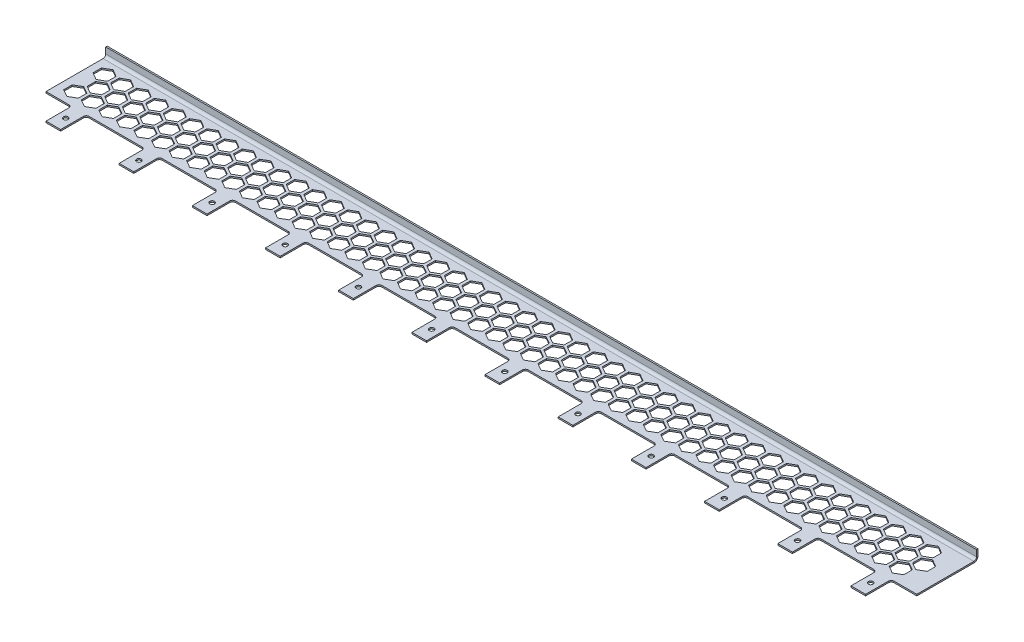
SolidWorks part; units mm, degrees
note: The reader was unsure of these and kept them because the rebuilt part matched: flange length of "Edge-Flange1".
ref_plane "Front Plane" through (0, 0, 0) normal (0, 0, 1) x (1, 0, 0)
ref_plane "Top Plane" through (0, 0, 0) normal (0, 1, 0) x (1, 0, 0)
ref_plane "Right Plane" through (0, 0, 0) normal (1, 0, 0) x (0, 0, -1)
sketch "Sketch1" plane through (0, 0, 0) normal (0, 1, 0) x (1, 0, 0)
  line L0 (29.5, 0) -> (65.5, 0)
  line L1 (0, 0) -> (15.5, 0)
  line L2 (0, 0) -> (0, 39)
  line L3 (0, 39) -> (595, 39)
  line L4 (595, 0) -> (595, 39)
  line L6 (17.5, -2) -> (17.5, -17.5)
  line L7 (17.5, -17.5) -> (27.5, -17.5)
  line L8 (27.5, -2) -> (27.5, -17.5)
  line L9 (67.5, -2) -> (67.5, -17.5)
  line L10 (67.5, -17.5) -> (77.5, -17.5)
  line L11 (77.5, -2) -> (77.5, -17.5)
  line L12 (117.5, -2) -> (117.5, -17.5)
  line L13 (117.5, -17.5) -> (127.5, -17.5)
  line L14 (127.5, -2) -> (127.5, -17.5)
  line L15 (167.5, -2) -> (167.5, -17.5)
  line L16 (167.5, -17.5) -> (177.5, -17.5)
  line L17 (177.5, -2) -> (177.5, -17.5)
  line L18 (217.5, -2) -> (217.5, -17.5)
  line L19 (217.5, -17.5) -> (227.5, -17.5)
  line L20 (227.5, -2) -> (227.5, -17.5)
  line L21 (267.5, -2) -> (267.5, -17.5)
  line L22 (267.5, -17.5) -> (277.5, -17.5)
  line L23 (277.5, -2) -> (277.5, -17.5)
  line L24 (317.5, -2) -> (317.5, -17.5)
  line L25 (317.5, -17.5) -> (327.5, -17.5)
  line L26 (327.5, -2) -> (327.5, -17.5)
  line L27 (367.5, -2) -> (367.5, -17.5)
  line L28 (367.5, -17.5) -> (377.5, -17.5)
  line L29 (377.5, -2) -> (377.5, -17.5)
  line L30 (417.5, -2) -> (417.5, -17.5)
  line L31 (417.5, -17.5) -> (427.5, -17.5)
  line L32 (427.5, -2) -> (427.5, -17.5)
  line L33 (467.5, -2) -> (467.5, -17.5)
  line L34 (467.5, -17.5) -> (477.5, -17.5)
  line L35 (477.5, -2) -> (477.5, -17.5)
  line L36 (517.5, -2) -> (517.5, -17.5)
  line L37 (517.5, -17.5) -> (527.5, -17.5)
  line L38 (527.5, -2) -> (527.5, -17.5)
  line L39 (567.5, -2) -> (567.5, -17.5)
  line L40 (567.5, -17.5) -> (577.5, -17.5)
  line L41 (577.5, -2) -> (577.5, -17.5)
  line L42 (79.5, 0) -> (115.5, 0)
  line L43 (129.5, 0) -> (165.5, 0)
  line L44 (179.5, 0) -> (215.5, 0)
  line L45 (229.5, 0) -> (265.5, 0)
  line L46 (279.5, 0) -> (315.5, 0)
  line L47 (329.5, 0) -> (365.5, 0)
  line L48 (379.5, 0) -> (415.5, 0)
  line L49 (429.5, 0) -> (465.5, 0)
  line L50 (479.5, 0) -> (515.5, 0)
  line L51 (529.5, 0) -> (565.5, 0)
  line L52 (579.5, 0) -> (595, 0)
  line L53 (22.5, -17.5) -> (22.5, 39) construction
  arc A0 (29.5, 0) -> (27.5, -2) centre (29.5, -2) ccw
  arc A1 (15.5, 0) -> (17.5, -2) centre (15.5, -2) cw
  arc A2 (79.5, 0) -> (77.5, -2) centre (79.5, -2) ccw
  arc A3 (65.5, 0) -> (67.5, -2) centre (65.5, -2) cw
  arc A4 (129.5, 0) -> (127.5, -2) centre (129.5, -2) ccw
  arc A5 (115.5, 0) -> (117.5, -2) centre (115.5, -2) cw
  arc A6 (179.5, 0) -> (177.5, -2) centre (179.5, -2) ccw
  arc A7 (165.5, 0) -> (167.5, -2) centre (165.5, -2) cw
  arc A8 (229.5, 0) -> (227.5, -2) centre (229.5, -2) ccw
  arc A9 (215.5, 0) -> (217.5, -2) centre (215.5, -2) cw
  arc A10 (279.5, 0) -> (277.5, -2) centre (279.5, -2) ccw
  arc A11 (265.5, 0) -> (267.5, -2) centre (265.5, -2) cw
  arc A12 (329.5, 0) -> (327.5, -2) centre (329.5, -2) ccw
  arc A13 (315.5, 0) -> (317.5, -2) centre (315.5, -2) cw
  arc A14 (379.5, 0) -> (377.5, -2) centre (379.5, -2) ccw
  arc A15 (365.5, 0) -> (367.5, -2) centre (365.5, -2) cw
  arc A16 (429.5, 0) -> (427.5, -2) centre (429.5, -2) ccw
  arc A17 (415.5, 0) -> (417.5, -2) centre (415.5, -2) cw
  arc A18 (479.5, 0) -> (477.5, -2) centre (479.5, -2) ccw
  arc A19 (465.5, 0) -> (467.5, -2) centre (465.5, -2) cw
  arc A20 (529.5, 0) -> (527.5, -2) centre (529.5, -2) ccw
  arc A21 (515.5, 0) -> (517.5, -2) centre (515.5, -2) cw
  arc A22 (579.5, 0) -> (577.5, -2) centre (579.5, -2) ccw
  arc A23 (565.5, 0) -> (567.5, -2) centre (565.5, -2) cw
  circle A24 centre (22.5, -9) radius 1.6
  circle A25 centre (72.5, -9) radius 1.6
  circle A26 centre (122.5, -9) radius 1.6
  circle A27 centre (172.5, -9) radius 1.6
  circle A28 centre (222.5, -9) radius 1.6
  circle A29 centre (272.5, -9) radius 1.6
  circle A30 centre (322.5, -9) radius 1.6
  circle A31 centre (372.5, -9) radius 1.6
  circle A32 centre (422.5, -9) radius 1.6
  circle A33 centre (472.5, -9) radius 1.6
  circle A34 centre (522.5, -9) radius 1.6
  circle A35 centre (572.5, -9) radius 1.6
  point P9 (22.5, -17.5)
  point P14 (17.5, 0)
  dimension "D6" = 2
  dimension "D8" = 9
  dimension "D9" = 3.2
  dimension "D1" = 595
  dimension "D2" = 39
  dimension "D3" = 10
  dimension "D4" = 17.5
  dimension "D5" = 22.5
  dimension "D7" = 12
  dimension "D10" = 12
base flange "Base-Flange2" sketch "Sketch1" thickness 1 reverse thickness direction no parameters "D1"=1.8
edge flange "Edge-Flange1" sketch "Sketch14" flange angle 90 flange length 7 flange position bend outside bend radius 1.8 thickness 1 relief rectangular parameters "D6"=10
sketch "Sketch14" plane through (0, 0, -39) normal (0, 0, -1) x (-1, 0, 0)
  line L0 (-595, 0) -> (0, 0) construction
  line L1 (-595, 0) -> (0, 0)
  line L2 (-595, 0) -> (-595, 6)
  line L3 (-595, 6) -> (0, 6)
  line L4 (0, 6) -> (0, 0)
bend "EdgeBend1" bend radius 1.8 bend angle 90 parameters "D5"=1
sketch "Sketch15" plane through (0, 0, 0) normal (0, 1, 0) x (1, 0, 0)
  line L0 (0, 0) -> (15.5, 0) construction
  line L1 (10, 4.2265) -> (15, 7.1132)
  line L2 (15, 7.1132) -> (15, 12.8868)
  line L3 (15, 12.8868) -> (10, 15.7735)
  line L4 (10, 15.7735) -> (5, 12.8868)
  line L5 (5, 12.8868) -> (5, 7.1132)
  line L6 (5, 7.1132) -> (10, 4.2265)
  line L7 (0, 39) -> (0, 0) construction
  line L8 (21.9375, 24.2268) -> (26.9685, 27.0592)
  line L9 (15.9823, 14.2265) -> (20.9911, 17.098)
  line L10 (20.9911, 17.098) -> (21.0088, 22.8714)
  line L11 (21.0088, 22.8714) -> (16.0177, 25.7735)
  line L12 (16.0177, 25.7735) -> (11.0089, 22.902)
  line L13 (11.0089, 22.902) -> (10.9912, 17.1286)
  line L14 (10.9912, 17.1286) -> (15.9823, 14.2265)
  line L15 (9.9375, 24.2268) -> (14.9685, 27.0592)
  line L16 (14.9685, 27.0592) -> (15.0311, 32.8324)
  line L17 (15.0311, 32.8324) -> (10.0627, 35.7732)
  line L18 (10.0627, 35.7732) -> (5.0317, 32.9408)
  line L19 (5.0317, 32.9408) -> (4.9691, 27.1676)
  line L20 (4.9691, 27.1676) -> (9.9375, 24.2268)
  line L21 (26.9685, 27.0592) -> (27.0311, 32.8324)
  line L22 (27.0311, 32.8324) -> (22.0627, 35.7732)
  line L23 (22.0627, 35.7732) -> (17.0317, 32.9408)
  line L24 (17.0317, 32.9408) -> (16.9691, 27.1676)
  line L25 (16.9691, 27.1676) -> (21.9375, 24.2268)
  line L26 (27.9823, 14.2265) -> (32.9911, 17.098)
  line L27 (32.9911, 17.098) -> (33.0088, 22.8714)
  line L28 (33.0088, 22.8714) -> (28.0177, 25.7735)
  line L29 (28.0177, 25.7735) -> (23.0089, 22.902)
  line L30 (23.0089, 22.902) -> (22.9912, 17.1286)
  line L31 (22.9912, 17.1286) -> (27.9823, 14.2265)
  line L32 (22, 4.2265) -> (27, 7.1132)
  line L33 (27, 7.1132) -> (27, 12.8868)
  line L34 (27, 12.8868) -> (22, 15.7735)
  line L35 (22, 15.7735) -> (17, 12.8868)
  line L36 (17, 12.8868) -> (17, 7.1132)
  line L37 (17, 7.1132) -> (22, 4.2265)
  line L38 (33.9375, 24.2268) -> (38.9685, 27.0592)
  line L39 (38.9685, 27.0592) -> (39.0311, 32.8324)
  line L40 (39.0311, 32.8324) -> (34.0627, 35.7732)
  line L41 (34.0627, 35.7732) -> (29.0317, 32.9408)
  line L42 (29.0317, 32.9408) -> (28.9691, 27.1676)
  line L43 (28.9691, 27.1676) -> (33.9375, 24.2268)
  line L44 (39.9823, 14.2265) -> (44.9911, 17.098)
  line L45 (44.9911, 17.098) -> (45.0088, 22.8714)
  line L46 (45.0088, 22.8714) -> (40.0177, 25.7735)
  line L47 (40.0177, 25.7735) -> (35.0089, 22.902)
  line L48 (35.0089, 22.902) -> (34.9912, 17.1286)
  line L49 (34.9912, 17.1286) -> (39.9823, 14.2265)
  line L50 (34, 4.2265) -> (39, 7.1132)
  line L51 (39, 7.1132) -> (39, 12.8868)
  line L52 (39, 12.8868) -> (34, 15.7735)
  line L53 (34, 15.7735) -> (29, 12.8868)
  line L54 (29, 12.8868) -> (29, 7.1132)
  line L55 (29, 7.1132) -> (34, 4.2265)
  line L56 (45.9375, 24.2268) -> (50.9685, 27.0592)
  line L57 (50.9685, 27.0592) -> (51.0311, 32.8324)
  line L58 (51.0311, 32.8324) -> (46.0627, 35.7732)
  line L59 (46.0627, 35.7732) -> (41.0317, 32.9408)
  line L60 (41.0317, 32.9408) -> (40.9691, 27.1676)
  line L61 (40.9691, 27.1676) -> (45.9375, 24.2268)
  line L62 (51.9823, 14.2265) -> (56.9911, 17.098)
  line L63 (56.9911, 17.098) -> (57.0088, 22.8714)
  line L64 (57.0088, 22.8714) -> (52.0177, 25.7735)
  line L65 (52.0177, 25.7735) -> (47.0089, 22.902)
  line L66 (47.0089, 22.902) -> (46.9912, 17.1286)
  line L67 (46.9912, 17.1286) -> (51.9823, 14.2265)
  line L68 (46, 4.2265) -> (51, 7.1132)
  line L69 (51, 7.1132) -> (51, 12.8868)
  line L70 (51, 12.8868) -> (46, 15.7735)
  line L71 (46, 15.7735) -> (41, 12.8868)
  line L72 (41, 12.8868) -> (41, 7.1132)
  line L73 (41, 7.1132) -> (46, 4.2265)
  line L74 (57.9375, 24.2268) -> (62.9685, 27.0592)
  line L75 (62.9685, 27.0592) -> (63.0311, 32.8324)
  line L76 (63.0311, 32.8324) -> (58.0627, 35.7732)
  line L77 (58.0627, 35.7732) -> (53.0317, 32.9408)
  line L78 (53.0317, 32.9408) -> (52.9691, 27.1676)
  line L79 (52.9691, 27.1676) -> (57.9375, 24.2268)
  line L80 (63.9823, 14.2265) -> (68.9911, 17.098)
  line L81 (68.9911, 17.098) -> (69.0088, 22.8714)
  line L82 (69.0088, 22.8714) -> (64.0177, 25.7735)
  line L83 (64.0177, 25.7735) -> (59.0089, 22.902)
  line L84 (59.0089, 22.902) -> (58.9912, 17.1286)
  line L85 (58.9912, 17.1286) -> (63.9823, 14.2265)
  line L86 (58, 4.2265) -> (63, 7.1132)
  line L87 (63, 7.1132) -> (63, 12.8868)
  line L88 (63, 12.8868) -> (58, 15.7735)
  line L89 (58, 15.7735) -> (53, 12.8868)
  line L90 (53, 12.8868) -> (53, 7.1132)
  line L91 (53, 7.1132) -> (58, 4.2265)
  line L92 (69.9375, 24.2268) -> (74.9685, 27.0592)
  line L93 (74.9685, 27.0592) -> (75.0311, 32.8324)
  line L94 (75.0311, 32.8324) -> (70.0627, 35.7732)
  line L95 (70.0627, 35.7732) -> (65.0317, 32.9408)
  line L96 (65.0317, 32.9408) -> (64.9691, 27.1676)
  line L97 (64.9691, 27.1676) -> (69.9375, 24.2268)
  line L98 (75.9823, 14.2265) -> (80.9911, 17.098)
  line L99 (80.9911, 17.098) -> (81.0088, 22.8714)
  line L100 (81.0088, 22.8714) -> (76.0177, 25.7735)
  line L101 (76.0177, 25.7735) -> (71.0089, 22.902)
  line L102 (71.0089, 22.902) -> (70.9912, 17.1286)
  line L103 (70.9912, 17.1286) -> (75.9823, 14.2265)
  line L104 (70, 4.2265) -> (75, 7.1132)
  line L105 (75, 7.1132) -> (75, 12.8868)
  line L106 (75, 12.8868) -> (70, 15.7735)
  line L107 (70, 15.7735) -> (65, 12.8868)
  line L108 (65, 12.8868) -> (65, 7.1132)
  line L109 (65, 7.1132) -> (70, 4.2265)
  line L110 (81.9375, 24.2268) -> (86.9685, 27.0592)
  line L111 (86.9685, 27.0592) -> (87.0311, 32.8324)
  line L112 (87.0311, 32.8324) -> (82.0627, 35.7732)
  line L113 (82.0627, 35.7732) -> (77.0317, 32.9408)
  line L114 (77.0317, 32.9408) -> (76.9691, 27.1676)
  line L115 (76.9691, 27.1676) -> (81.9375, 24.2268)
  line L116 (87.9823, 14.2265) -> (92.9911, 17.098)
  line L117 (92.9911, 17.098) -> (93.0088, 22.8714)
  line L118 (93.0088, 22.8714) -> (88.0177, 25.7735)
  line L119 (88.0177, 25.7735) -> (83.0089, 22.902)
  line L120 (83.0089, 22.902) -> (82.9912, 17.1286)
  line L121 (82.9912, 17.1286) -> (87.9823, 14.2265)
  line L122 (82, 4.2265) -> (87, 7.1132)
  line L123 (87, 7.1132) -> (87, 12.8868)
  line L124 (87, 12.8868) -> (82, 15.7735)
  line L125 (82, 15.7735) -> (77, 12.8868)
  line L126 (77, 12.8868) -> (77, 7.1132)
  line L127 (77, 7.1132) -> (82, 4.2265)
  line L128 (93.9375, 24.2268) -> (98.9685, 27.0592)
  line L129 (98.9685, 27.0592) -> (99.0311, 32.8324)
  line L130 (99.0311, 32.8324) -> (94.0627, 35.7732)
  line L131 (94.0627, 35.7732) -> (89.0317, 32.9408)
  line L132 (89.0317, 32.9408) -> (88.9691, 27.1676)
  line L133 (88.9691, 27.1676) -> (93.9375, 24.2268)
  line L134 (99.9823, 14.2265) -> (104.9911, 17.098)
  line L135 (104.9911, 17.098) -> (105.0088, 22.8714)
  line L136 (105.0088, 22.8714) -> (100.0177, 25.7735)
  line L137 (100.0177, 25.7735) -> (95.0089, 22.902)
  line L138 (95.0089, 22.902) -> (94.9912, 17.1286)
  line L139 (94.9912, 17.1286) -> (99.9823, 14.2265)
  line L140 (94, 4.2265) -> (99, 7.1132)
  line L141 (99, 7.1132) -> (99, 12.8868)
  line L142 (99, 12.8868) -> (94, 15.7735)
  line L143 (94, 15.7735) -> (89, 12.8868)
  line L144 (89, 12.8868) -> (89, 7.1132)
  line L145 (89, 7.1132) -> (94, 4.2265)
  line L146 (105.9375, 24.2268) -> (110.9685, 27.0592)
  line L147 (110.9685, 27.0592) -> (111.0311, 32.8324)
  line L148 (111.0311, 32.8324) -> (106.0627, 35.7732)
  line L149 (106.0627, 35.7732) -> (101.0317, 32.9408)
  line L150 (101.0317, 32.9408) -> (100.9691, 27.1676)
  line L151 (100.9691, 27.1676) -> (105.9375, 24.2268)
  line L152 (111.9823, 14.2265) -> (116.9911, 17.098)
  line L153 (116.9911, 17.098) -> (117.0088, 22.8714)
  line L154 (117.0088, 22.8714) -> (112.0177, 25.7735)
  line L155 (112.0177, 25.7735) -> (107.0089, 22.902)
  line L156 (107.0089, 22.902) -> (106.9912, 17.1286)
  line L157 (106.9912, 17.1286) -> (111.9823, 14.2265)
  line L158 (106, 4.2265) -> (111, 7.1132)
  line L159 (111, 7.1132) -> (111, 12.8868)
  line L160 (111, 12.8868) -> (106, 15.7735)
  line L161 (106, 15.7735) -> (101, 12.8868)
  line L162 (101, 12.8868) -> (101, 7.1132)
  line L163 (101, 7.1132) -> (106, 4.2265)
  line L164 (117.9375, 24.2268) -> (122.9685, 27.0592)
  line L165 (122.9685, 27.0592) -> (123.0311, 32.8324)
  line L166 (123.0311, 32.8324) -> (118.0627, 35.7732)
  line L167 (118.0627, 35.7732) -> (113.0317, 32.9408)
  line L168 (113.0317, 32.9408) -> (112.9691, 27.1676)
  line L169 (112.9691, 27.1676) -> (117.9375, 24.2268)
  line L170 (123.9823, 14.2265) -> (128.9911, 17.098)
  line L171 (128.9911, 17.098) -> (129.0088, 22.8714)
  line L172 (129.0088, 22.8714) -> (124.0177, 25.7735)
  line L173 (124.0177, 25.7735) -> (119.0089, 22.902)
  line L174 (119.0089, 22.902) -> (118.9912, 17.1286)
  line L175 (118.9912, 17.1286) -> (123.9823, 14.2265)
  line L176 (118, 4.2265) -> (123, 7.1132)
  line L177 (123, 7.1132) -> (123, 12.8868)
  line L178 (123, 12.8868) -> (118, 15.7735)
  line L179 (118, 15.7735) -> (113, 12.8868)
  line L180 (113, 12.8868) -> (113, 7.1132)
  line L181 (113, 7.1132) -> (118, 4.2265)
  line L182 (129.9375, 24.2268) -> (134.9685, 27.0592)
  line L183 (134.9685, 27.0592) -> (135.0311, 32.8324)
  line L184 (135.0311, 32.8324) -> (130.0627, 35.7732)
  line L185 (130.0627, 35.7732) -> (125.0317, 32.9408)
  line L186 (125.0317, 32.9408) -> (124.9691, 27.1676)
  line L187 (124.9691, 27.1676) -> (129.9375, 24.2268)
  line L188 (135.9823, 14.2265) -> (140.9911, 17.098)
  line L189 (140.9911, 17.098) -> (141.0088, 22.8714)
  line L190 (141.0088, 22.8714) -> (136.0177, 25.7735)
  line L191 (136.0177, 25.7735) -> (131.0089, 22.902)
  line L192 (131.0089, 22.902) -> (130.9912, 17.1286)
  line L193 (130.9912, 17.1286) -> (135.9823, 14.2265)
  line L194 (130, 4.2265) -> (135, 7.1132)
  line L195 (135, 7.1132) -> (135, 12.8868)
  line L196 (135, 12.8868) -> (130, 15.7735)
  line L197 (130, 15.7735) -> (125, 12.8868)
  line L198 (125, 12.8868) -> (125, 7.1132)
  line L199 (125, 7.1132) -> (130, 4.2265)
  line L200 (141.9375, 24.2268) -> (146.9685, 27.0592)
  line L201 (146.9685, 27.0592) -> (147.0311, 32.8324)
  line L202 (147.0311, 32.8324) -> (142.0627, 35.7732)
  line L203 (142.0627, 35.7732) -> (137.0317, 32.9408)
  line L204 (137.0317, 32.9408) -> (136.9691, 27.1676)
  line L205 (136.9691, 27.1676) -> (141.9375, 24.2268)
  line L206 (147.9823, 14.2265) -> (152.9911, 17.098)
  line L207 (152.9911, 17.098) -> (153.0088, 22.8714)
  line L208 (153.0088, 22.8714) -> (148.0177, 25.7735)
  line L209 (148.0177, 25.7735) -> (143.0089, 22.902)
  line L210 (143.0089, 22.902) -> (142.9912, 17.1286)
  line L211 (142.9912, 17.1286) -> (147.9823, 14.2265)
  line L212 (142, 4.2265) -> (147, 7.1132)
  line L213 (147, 7.1132) -> (147, 12.8868)
  line L214 (147, 12.8868) -> (142, 15.7735)
  line L215 (142, 15.7735) -> (137, 12.8868)
  line L216 (137, 12.8868) -> (137, 7.1132)
  line L217 (137, 7.1132) -> (142, 4.2265)
  line L218 (153.9375, 24.2268) -> (158.9685, 27.0592)
  line L219 (158.9685, 27.0592) -> (159.0311, 32.8324)
  line L220 (159.0311, 32.8324) -> (154.0627, 35.7732)
  line L221 (154.0627, 35.7732) -> (149.0317, 32.9408)
  line L222 (149.0317, 32.9408) -> (148.9691, 27.1676)
  line L223 (148.9691, 27.1676) -> (153.9375, 24.2268)
  line L224 (159.9823, 14.2265) -> (164.9911, 17.098)
  line L225 (164.9911, 17.098) -> (165.0088, 22.8714)
  line L226 (165.0088, 22.8714) -> (160.0177, 25.7735)
  line L227 (160.0177, 25.7735) -> (155.0089, 22.902)
  line L228 (155.0089, 22.902) -> (154.9912, 17.1286)
  line L229 (154.9912, 17.1286) -> (159.9823, 14.2265)
  line L230 (154, 4.2265) -> (159, 7.1132)
  line L231 (159, 7.1132) -> (159, 12.8868)
  line L232 (159, 12.8868) -> (154, 15.7735)
  line L233 (154, 15.7735) -> (149, 12.8868)
  line L234 (149, 12.8868) -> (149, 7.1132)
  line L235 (149, 7.1132) -> (154, 4.2265)
  line L236 (165.9375, 24.2268) -> (170.9685, 27.0592)
  line L237 (170.9685, 27.0592) -> (171.0311, 32.8324)
  line L238 (171.0311, 32.8324) -> (166.0627, 35.7732)
  line L239 (166.0627, 35.7732) -> (161.0317, 32.9408)
  line L240 (161.0317, 32.9408) -> (160.9691, 27.1676)
  line L241 (160.9691, 27.1676) -> (165.9375, 24.2268)
  line L242 (171.9823, 14.2265) -> (176.9911, 17.098)
  line L243 (176.9911, 17.098) -> (177.0088, 22.8714)
  line L244 (177.0088, 22.8714) -> (172.0177, 25.7735)
  line L245 (172.0177, 25.7735) -> (167.0089, 22.902)
  line L246 (167.0089, 22.902) -> (166.9912, 17.1286)
  line L247 (166.9912, 17.1286) -> (171.9823, 14.2265)
  line L248 (166, 4.2265) -> (171, 7.1132)
  line L249 (171, 7.1132) -> (171, 12.8868)
  line L250 (171, 12.8868) -> (166, 15.7735)
  line L251 (166, 15.7735) -> (161, 12.8868)
  line L252 (161, 12.8868) -> (161, 7.1132)
  line L253 (161, 7.1132) -> (166, 4.2265)
  line L254 (177.9375, 24.2268) -> (182.9685, 27.0592)
  line L255 (182.9685, 27.0592) -> (183.0311, 32.8324)
  line L256 (183.0311, 32.8324) -> (178.0627, 35.7732)
  line L257 (178.0627, 35.7732) -> (173.0317, 32.9408)
  line L258 (173.0317, 32.9408) -> (172.9691, 27.1676)
  line L259 (172.9691, 27.1676) -> (177.9375, 24.2268)
  line L260 (183.9823, 14.2265) -> (188.9911, 17.098)
  line L261 (188.9911, 17.098) -> (189.0088, 22.8714)
  line L262 (189.0088, 22.8714) -> (184.0177, 25.7735)
  line L263 (184.0177, 25.7735) -> (179.0089, 22.902)
  line L264 (179.0089, 22.902) -> (178.9912, 17.1286)
  line L265 (178.9912, 17.1286) -> (183.9823, 14.2265)
  line L266 (178, 4.2265) -> (183, 7.1132)
  line L267 (183, 7.1132) -> (183, 12.8868)
  line L268 (183, 12.8868) -> (178, 15.7735)
  line L269 (178, 15.7735) -> (173, 12.8868)
  line L270 (173, 12.8868) -> (173, 7.1132)
  line L271 (173, 7.1132) -> (178, 4.2265)
  line L272 (189.9375, 24.2268) -> (194.9685, 27.0592)
  line L273 (194.9685, 27.0592) -> (195.0311, 32.8324)
  line L274 (195.0311, 32.8324) -> (190.0627, 35.7732)
  line L275 (190.0627, 35.7732) -> (185.0317, 32.9408)
  line L276 (185.0317, 32.9408) -> (184.9691, 27.1676)
  line L277 (184.9691, 27.1676) -> (189.9375, 24.2268)
  line L278 (195.9823, 14.2265) -> (200.9911, 17.098)
  line L279 (200.9911, 17.098) -> (201.0088, 22.8714)
  line L280 (201.0088, 22.8714) -> (196.0177, 25.7735)
  line L281 (196.0177, 25.7735) -> (191.0089, 22.902)
  line L282 (191.0089, 22.902) -> (190.9912, 17.1286)
  line L283 (190.9912, 17.1286) -> (195.9823, 14.2265)
  line L284 (190, 4.2265) -> (195, 7.1132)
  line L285 (195, 7.1132) -> (195, 12.8868)
  line L286 (195, 12.8868) -> (190, 15.7735)
  line L287 (190, 15.7735) -> (185, 12.8868)
  line L288 (185, 12.8868) -> (185, 7.1132)
  line L289 (185, 7.1132) -> (190, 4.2265)
  line L290 (201.9375, 24.2268) -> (206.9685, 27.0592)
  line L291 (206.9685, 27.0592) -> (207.0311, 32.8324)
  line L292 (207.0311, 32.8324) -> (202.0627, 35.7732)
  line L293 (202.0627, 35.7732) -> (197.0317, 32.9408)
  line L294 (197.0317, 32.9408) -> (196.9691, 27.1676)
  line L295 (196.9691, 27.1676) -> (201.9375, 24.2268)
  line L296 (207.9823, 14.2265) -> (212.9911, 17.098)
  line L297 (212.9911, 17.098) -> (213.0088, 22.8714)
  line L298 (213.0088, 22.8714) -> (208.0177, 25.7735)
  line L299 (208.0177, 25.7735) -> (203.0089, 22.902)
  line L300 (203.0089, 22.902) -> (202.9912, 17.1286)
  line L301 (202.9912, 17.1286) -> (207.9823, 14.2265)
  line L302 (202, 4.2265) -> (207, 7.1132)
  line L303 (207, 7.1132) -> (207, 12.8868)
  line L304 (207, 12.8868) -> (202, 15.7735)
  line L305 (202, 15.7735) -> (197, 12.8868)
  line L306 (197, 12.8868) -> (197, 7.1132)
  line L307 (197, 7.1132) -> (202, 4.2265)
  line L308 (213.9375, 24.2268) -> (218.9685, 27.0592)
  line L309 (218.9685, 27.0592) -> (219.0311, 32.8324)
  line L310 (219.0311, 32.8324) -> (214.0627, 35.7732)
  line L311 (214.0627, 35.7732) -> (209.0317, 32.9408)
  line L312 (209.0317, 32.9408) -> (208.9691, 27.1676)
  line L313 (208.9691, 27.1676) -> (213.9375, 24.2268)
  line L314 (219.9823, 14.2265) -> (224.9911, 17.098)
  line L315 (224.9911, 17.098) -> (225.0088, 22.8714)
  line L316 (225.0088, 22.8714) -> (220.0177, 25.7735)
  line L317 (220.0177, 25.7735) -> (215.0089, 22.902)
  line L318 (215.0089, 22.902) -> (214.9912, 17.1286)
  line L319 (214.9912, 17.1286) -> (219.9823, 14.2265)
  line L320 (214, 4.2265) -> (219, 7.1132)
  line L321 (219, 7.1132) -> (219, 12.8868)
  line L322 (219, 12.8868) -> (214, 15.7735)
  line L323 (214, 15.7735) -> (209, 12.8868)
  line L324 (209, 12.8868) -> (209, 7.1132)
  line L325 (209, 7.1132) -> (214, 4.2265)
  line L326 (225.9375, 24.2268) -> (230.9685, 27.0592)
  line L327 (230.9685, 27.0592) -> (231.0311, 32.8324)
  line L328 (231.0311, 32.8324) -> (226.0627, 35.7732)
  line L329 (226.0627, 35.7732) -> (221.0317, 32.9408)
  line L330 (221.0317, 32.9408) -> (220.9691, 27.1676)
  line L331 (220.9691, 27.1676) -> (225.9375, 24.2268)
  line L332 (231.9823, 14.2265) -> (236.9911, 17.098)
  line L333 (236.9911, 17.098) -> (237.0088, 22.8714)
  line L334 (237.0088, 22.8714) -> (232.0177, 25.7735)
  line L335 (232.0177, 25.7735) -> (227.0089, 22.902)
  line L336 (227.0089, 22.902) -> (226.9912, 17.1286)
  line L337 (226.9912, 17.1286) -> (231.9823, 14.2265)
  line L338 (226, 4.2265) -> (231, 7.1132)
  line L339 (231, 7.1132) -> (231, 12.8868)
  line L340 (231, 12.8868) -> (226, 15.7735)
  line L341 (226, 15.7735) -> (221, 12.8868)
  line L342 (221, 12.8868) -> (221, 7.1132)
  line L343 (221, 7.1132) -> (226, 4.2265)
  line L344 (237.9375, 24.2268) -> (242.9685, 27.0592)
  line L345 (242.9685, 27.0592) -> (243.0311, 32.8324)
  line L346 (243.0311, 32.8324) -> (238.0627, 35.7732)
  line L347 (238.0627, 35.7732) -> (233.0317, 32.9408)
  line L348 (233.0317, 32.9408) -> (232.9691, 27.1676)
  line L349 (232.9691, 27.1676) -> (237.9375, 24.2268)
  line L350 (243.9823, 14.2265) -> (248.9911, 17.098)
  line L351 (248.9911, 17.098) -> (249.0088, 22.8714)
  line L352 (249.0088, 22.8714) -> (244.0177, 25.7735)
  line L353 (244.0177, 25.7735) -> (239.0089, 22.902)
  line L354 (239.0089, 22.902) -> (238.9912, 17.1286)
  line L355 (238.9912, 17.1286) -> (243.9823, 14.2265)
  line L356 (238, 4.2265) -> (243, 7.1132)
  line L357 (243, 7.1132) -> (243, 12.8868)
  line L358 (243, 12.8868) -> (238, 15.7735)
  line L359 (238, 15.7735) -> (233, 12.8868)
  line L360 (233, 12.8868) -> (233, 7.1132)
  line L361 (233, 7.1132) -> (238, 4.2265)
  line L362 (249.9375, 24.2268) -> (254.9685, 27.0592)
  line L363 (254.9685, 27.0592) -> (255.0311, 32.8324)
  line L364 (255.0311, 32.8324) -> (250.0627, 35.7732)
  line L365 (250.0627, 35.7732) -> (245.0317, 32.9408)
  line L366 (245.0317, 32.9408) -> (244.9691, 27.1676)
  line L367 (244.9691, 27.1676) -> (249.9375, 24.2268)
  line L368 (255.9823, 14.2265) -> (260.9911, 17.098)
  line L369 (260.9911, 17.098) -> (261.0088, 22.8714)
  line L370 (261.0088, 22.8714) -> (256.0177, 25.7735)
  line L371 (256.0177, 25.7735) -> (251.0089, 22.902)
  line L372 (251.0089, 22.902) -> (250.9912, 17.1286)
  line L373 (250.9912, 17.1286) -> (255.9823, 14.2265)
  line L374 (250, 4.2265) -> (255, 7.1132)
  line L375 (255, 7.1132) -> (255, 12.8868)
  line L376 (255, 12.8868) -> (250, 15.7735)
  line L377 (250, 15.7735) -> (245, 12.8868)
  line L378 (245, 12.8868) -> (245, 7.1132)
  line L379 (245, 7.1132) -> (250, 4.2265)
  line L380 (261.9375, 24.2268) -> (266.9685, 27.0592)
  line L381 (266.9685, 27.0592) -> (267.0311, 32.8324)
  line L382 (267.0311, 32.8324) -> (262.0627, 35.7732)
  line L383 (262.0627, 35.7732) -> (257.0317, 32.9408)
  line L384 (257.0317, 32.9408) -> (256.9691, 27.1676)
  line L385 (256.9691, 27.1676) -> (261.9375, 24.2268)
  line L386 (267.9823, 14.2265) -> (272.9911, 17.098)
  line L387 (272.9911, 17.098) -> (273.0088, 22.8714)
  line L388 (273.0088, 22.8714) -> (268.0177, 25.7735)
  line L389 (268.0177, 25.7735) -> (263.0089, 22.902)
  line L390 (263.0089, 22.902) -> (262.9912, 17.1286)
  line L391 (262.9912, 17.1286) -> (267.9823, 14.2265)
  line L392 (262, 4.2265) -> (267, 7.1132)
  line L393 (267, 7.1132) -> (267, 12.8868)
  line L394 (267, 12.8868) -> (262, 15.7735)
  line L395 (262, 15.7735) -> (257, 12.8868)
  line L396 (257, 12.8868) -> (257, 7.1132)
  line L397 (257, 7.1132) -> (262, 4.2265)
  line L398 (273.9375, 24.2268) -> (278.9685, 27.0592)
  line L399 (278.9685, 27.0592) -> (279.0311, 32.8324)
  line L400 (279.0311, 32.8324) -> (274.0627, 35.7732)
  line L401 (274.0627, 35.7732) -> (269.0317, 32.9408)
  line L402 (269.0317, 32.9408) -> (268.9691, 27.1676)
  line L403 (268.9691, 27.1676) -> (273.9375, 24.2268)
  line L404 (279.9823, 14.2265) -> (284.9911, 17.098)
  line L405 (284.9911, 17.098) -> (285.0088, 22.8714)
  line L406 (285.0088, 22.8714) -> (280.0177, 25.7735)
  line L407 (280.0177, 25.7735) -> (275.0089, 22.902)
  line L408 (275.0089, 22.902) -> (274.9912, 17.1286)
  line L409 (274.9912, 17.1286) -> (279.9823, 14.2265)
  line L410 (274, 4.2265) -> (279, 7.1132)
  line L411 (279, 7.1132) -> (279, 12.8868)
  line L412 (279, 12.8868) -> (274, 15.7735)
  line L413 (274, 15.7735) -> (269, 12.8868)
  line L414 (269, 12.8868) -> (269, 7.1132)
  line L415 (269, 7.1132) -> (274, 4.2265)
  line L416 (285.9375, 24.2268) -> (290.9685, 27.0592)
  line L417 (290.9685, 27.0592) -> (291.0311, 32.8324)
  line L418 (291.0311, 32.8324) -> (286.0627, 35.7732)
  line L419 (286.0627, 35.7732) -> (281.0317, 32.9408)
  line L420 (281.0317, 32.9408) -> (280.9691, 27.1676)
  line L421 (280.9691, 27.1676) -> (285.9375, 24.2268)
  line L422 (291.9823, 14.2265) -> (296.9911, 17.098)
  line L423 (296.9911, 17.098) -> (297.0088, 22.8714)
  line L424 (297.0088, 22.8714) -> (292.0177, 25.7735)
  line L425 (292.0177, 25.7735) -> (287.0089, 22.902)
  line L426 (287.0089, 22.902) -> (286.9912, 17.1286)
  line L427 (286.9912, 17.1286) -> (291.9823, 14.2265)
  line L428 (286, 4.2265) -> (291, 7.1132)
  line L429 (291, 7.1132) -> (291, 12.8868)
  line L430 (291, 12.8868) -> (286, 15.7735)
  line L431 (286, 15.7735) -> (281, 12.8868)
  line L432 (281, 12.8868) -> (281, 7.1132)
  line L433 (281, 7.1132) -> (286, 4.2265)
  line L434 (297.9375, 24.2268) -> (302.9685, 27.0592)
  line L435 (302.9685, 27.0592) -> (303.0311, 32.8324)
  line L436 (303.0311, 32.8324) -> (298.0627, 35.7732)
  line L437 (298.0627, 35.7732) -> (293.0317, 32.9408)
  line L438 (293.0317, 32.9408) -> (292.9691, 27.1676)
  line L439 (292.9691, 27.1676) -> (297.9375, 24.2268)
  line L440 (303.9823, 14.2265) -> (308.9911, 17.098)
  line L441 (308.9911, 17.098) -> (309.0088, 22.8714)
  line L442 (309.0088, 22.8714) -> (304.0177, 25.7735)
  line L443 (304.0177, 25.7735) -> (299.0089, 22.902)
  line L444 (299.0089, 22.902) -> (298.9912, 17.1286)
  line L445 (298.9912, 17.1286) -> (303.9823, 14.2265)
  line L446 (298, 4.2265) -> (303, 7.1132)
  line L447 (303, 7.1132) -> (303, 12.8868)
  line L448 (303, 12.8868) -> (298, 15.7735)
  line L449 (298, 15.7735) -> (293, 12.8868)
  line L450 (293, 12.8868) -> (293, 7.1132)
  line L451 (293, 7.1132) -> (298, 4.2265)
  line L452 (309.9375, 24.2268) -> (314.9685, 27.0592)
  line L453 (314.9685, 27.0592) -> (315.0311, 32.8324)
  line L454 (315.0311, 32.8324) -> (310.0627, 35.7732)
  line L455 (310.0627, 35.7732) -> (305.0317, 32.9408)
  line L456 (305.0317, 32.9408) -> (304.9691, 27.1676)
  line L457 (304.9691, 27.1676) -> (309.9375, 24.2268)
  line L458 (315.9823, 14.2265) -> (320.9911, 17.098)
  line L459 (320.9911, 17.098) -> (321.0088, 22.8714)
  line L460 (321.0088, 22.8714) -> (316.0177, 25.7735)
  line L461 (316.0177, 25.7735) -> (311.0089, 22.902)
  line L462 (311.0089, 22.902) -> (310.9912, 17.1286)
  line L463 (310.9912, 17.1286) -> (315.9823, 14.2265)
  line L464 (310, 4.2265) -> (315, 7.1132)
  line L465 (315, 7.1132) -> (315, 12.8868)
  line L466 (315, 12.8868) -> (310, 15.7735)
  line L467 (310, 15.7735) -> (305, 12.8868)
  line L468 (305, 12.8868) -> (305, 7.1132)
  line L469 (305, 7.1132) -> (310, 4.2265)
  line L470 (321.9375, 24.2268) -> (326.9685, 27.0592)
  line L471 (326.9685, 27.0592) -> (327.0311, 32.8324)
  line L472 (327.0311, 32.8324) -> (322.0627, 35.7732)
  line L473 (322.0627, 35.7732) -> (317.0317, 32.9408)
  line L474 (317.0317, 32.9408) -> (316.9691, 27.1676)
  line L475 (316.9691, 27.1676) -> (321.9375, 24.2268)
  line L476 (327.9823, 14.2265) -> (332.9911, 17.098)
  line L477 (332.9911, 17.098) -> (333.0088, 22.8714)
  line L478 (333.0088, 22.8714) -> (328.0177, 25.7735)
  line L479 (328.0177, 25.7735) -> (323.0089, 22.902)
  line L480 (323.0089, 22.902) -> (322.9912, 17.1286)
  line L481 (322.9912, 17.1286) -> (327.9823, 14.2265)
  line L482 (322, 4.2265) -> (327, 7.1132)
  line L483 (327, 7.1132) -> (327, 12.8868)
  line L484 (327, 12.8868) -> (322, 15.7735)
  line L485 (322, 15.7735) -> (317, 12.8868)
  line L486 (317, 12.8868) -> (317, 7.1132)
  line L487 (317, 7.1132) -> (322, 4.2265)
  line L488 (333.9375, 24.2268) -> (338.9685, 27.0592)
  line L489 (338.9685, 27.0592) -> (339.0311, 32.8324)
  line L490 (339.0311, 32.8324) -> (334.0627, 35.7732)
  line L491 (334.0627, 35.7732) -> (329.0317, 32.9408)
  line L492 (329.0317, 32.9408) -> (328.9691, 27.1676)
  line L493 (328.9691, 27.1676) -> (333.9375, 24.2268)
  line L494 (339.9823, 14.2265) -> (344.9911, 17.098)
  line L495 (344.9911, 17.098) -> (345.0088, 22.8714)
  line L496 (345.0088, 22.8714) -> (340.0177, 25.7735)
  line L497 (340.0177, 25.7735) -> (335.0089, 22.902)
  line L498 (335.0089, 22.902) -> (334.9912, 17.1286)
  line L499 (334.9912, 17.1286) -> (339.9823, 14.2265)
  line L500 (334, 4.2265) -> (339, 7.1132)
  line L501 (339, 7.1132) -> (339, 12.8868)
  line L502 (339, 12.8868) -> (334, 15.7735)
  line L503 (334, 15.7735) -> (329, 12.8868)
  line L504 (329, 12.8868) -> (329, 7.1132)
  line L505 (329, 7.1132) -> (334, 4.2265)
  line L506 (345.9375, 24.2268) -> (350.9685, 27.0592)
  line L507 (350.9685, 27.0592) -> (351.0311, 32.8324)
  line L508 (351.0311, 32.8324) -> (346.0627, 35.7732)
  line L509 (346.0627, 35.7732) -> (341.0317, 32.9408)
  line L510 (341.0317, 32.9408) -> (340.9691, 27.1676)
  line L511 (340.9691, 27.1676) -> (345.9375, 24.2268)
  line L512 (351.9823, 14.2265) -> (356.9911, 17.098)
  line L513 (356.9911, 17.098) -> (357.0088, 22.8714)
  line L514 (357.0088, 22.8714) -> (352.0177, 25.7735)
  line L515 (352.0177, 25.7735) -> (347.0089, 22.902)
  line L516 (347.0089, 22.902) -> (346.9912, 17.1286)
  line L517 (346.9912, 17.1286) -> (351.9823, 14.2265)
  line L518 (346, 4.2265) -> (351, 7.1132)
  line L519 (351, 7.1132) -> (351, 12.8868)
  line L520 (351, 12.8868) -> (346, 15.7735)
  line L521 (346, 15.7735) -> (341, 12.8868)
  line L522 (341, 12.8868) -> (341, 7.1132)
  line L523 (341, 7.1132) -> (346, 4.2265)
  line L524 (357.9375, 24.2268) -> (362.9685, 27.0592)
  line L525 (362.9685, 27.0592) -> (363.0311, 32.8324)
  line L526 (363.0311, 32.8324) -> (358.0627, 35.7732)
  line L527 (358.0627, 35.7732) -> (353.0317, 32.9408)
  line L528 (353.0317, 32.9408) -> (352.9691, 27.1676)
  line L529 (352.9691, 27.1676) -> (357.9375, 24.2268)
  line L530 (363.9823, 14.2265) -> (368.9911, 17.098)
  line L531 (368.9911, 17.098) -> (369.0088, 22.8714)
  line L532 (369.0088, 22.8714) -> (364.0177, 25.7735)
  line L533 (364.0177, 25.7735) -> (359.0089, 22.902)
  line L534 (359.0089, 22.902) -> (358.9912, 17.1286)
  line L535 (358.9912, 17.1286) -> (363.9823, 14.2265)
  line L536 (358, 4.2265) -> (363, 7.1132)
  line L537 (363, 7.1132) -> (363, 12.8868)
  line L538 (363, 12.8868) -> (358, 15.7735)
  line L539 (358, 15.7735) -> (353, 12.8868)
  line L540 (353, 12.8868) -> (353, 7.1132)
  line L541 (353, 7.1132) -> (358, 4.2265)
  line L542 (369.9375, 24.2268) -> (374.9685, 27.0592)
  line L543 (374.9685, 27.0592) -> (375.0311, 32.8324)
  line L544 (375.0311, 32.8324) -> (370.0627, 35.7732)
  line L545 (370.0627, 35.7732) -> (365.0317, 32.9408)
  line L546 (365.0317, 32.9408) -> (364.9691, 27.1676)
  line L547 (364.9691, 27.1676) -> (369.9375, 24.2268)
  line L548 (375.9823, 14.2265) -> (380.9911, 17.098)
  line L549 (380.9911, 17.098) -> (381.0088, 22.8714)
  line L550 (381.0088, 22.8714) -> (376.0177, 25.7735)
  line L551 (376.0177, 25.7735) -> (371.0089, 22.902)
  line L552 (371.0089, 22.902) -> (370.9912, 17.1286)
  line L553 (370.9912, 17.1286) -> (375.9823, 14.2265)
  line L554 (370, 4.2265) -> (375, 7.1132)
  line L555 (375, 7.1132) -> (375, 12.8868)
  line L556 (375, 12.8868) -> (370, 15.7735)
  line L557 (370, 15.7735) -> (365, 12.8868)
  line L558 (365, 12.8868) -> (365, 7.1132)
  line L559 (365, 7.1132) -> (370, 4.2265)
  line L560 (381.9375, 24.2268) -> (386.9685, 27.0592)
  line L561 (386.9685, 27.0592) -> (387.0311, 32.8324)
  line L562 (387.0311, 32.8324) -> (382.0627, 35.7732)
  line L563 (382.0627, 35.7732) -> (377.0317, 32.9408)
  line L564 (377.0317, 32.9408) -> (376.9691, 27.1676)
  line L565 (376.9691, 27.1676) -> (381.9375, 24.2268)
  line L566 (387.9823, 14.2265) -> (392.9911, 17.098)
  line L567 (392.9911, 17.098) -> (393.0088, 22.8714)
  line L568 (393.0088, 22.8714) -> (388.0177, 25.7735)
  line L569 (388.0177, 25.7735) -> (383.0089, 22.902)
  line L570 (383.0089, 22.902) -> (382.9912, 17.1286)
  line L571 (382.9912, 17.1286) -> (387.9823, 14.2265)
  line L572 (382, 4.2265) -> (387, 7.1132)
  line L573 (387, 7.1132) -> (387, 12.8868)
  line L574 (387, 12.8868) -> (382, 15.7735)
  line L575 (382, 15.7735) -> (377, 12.8868)
  line L576 (377, 12.8868) -> (377, 7.1132)
  line L577 (377, 7.1132) -> (382, 4.2265)
  line L578 (393.9375, 24.2268) -> (398.9685, 27.0592)
  line L579 (398.9685, 27.0592) -> (399.0311, 32.8324)
  line L580 (399.0311, 32.8324) -> (394.0627, 35.7732)
  line L581 (394.0627, 35.7732) -> (389.0317, 32.9408)
  line L582 (389.0317, 32.9408) -> (388.9691, 27.1676)
  line L583 (388.9691, 27.1676) -> (393.9375, 24.2268)
  line L584 (399.9823, 14.2265) -> (404.9911, 17.098)
  line L585 (404.9911, 17.098) -> (405.0088, 22.8714)
  line L586 (405.0088, 22.8714) -> (400.0177, 25.7735)
  line L587 (400.0177, 25.7735) -> (395.0089, 22.902)
  line L588 (395.0089, 22.902) -> (394.9912, 17.1286)
  line L589 (394.9912, 17.1286) -> (399.9823, 14.2265)
  line L590 (394, 4.2265) -> (399, 7.1132)
  line L591 (399, 7.1132) -> (399, 12.8868)
  line L592 (399, 12.8868) -> (394, 15.7735)
  line L593 (394, 15.7735) -> (389, 12.8868)
  line L594 (389, 12.8868) -> (389, 7.1132)
  line L595 (389, 7.1132) -> (394, 4.2265)
  line L596 (405.9375, 24.2268) -> (410.9685, 27.0592)
  line L597 (410.9685, 27.0592) -> (411.0311, 32.8324)
  line L598 (411.0311, 32.8324) -> (406.0627, 35.7732)
  line L599 (406.0627, 35.7732) -> (401.0317, 32.9408)
  line L600 (401.0317, 32.9408) -> (400.9691, 27.1676)
  line L601 (400.9691, 27.1676) -> (405.9375, 24.2268)
  line L602 (411.9823, 14.2265) -> (416.9911, 17.098)
  line L603 (416.9911, 17.098) -> (417.0088, 22.8714)
  line L604 (417.0088, 22.8714) -> (412.0177, 25.7735)
  line L605 (412.0177, 25.7735) -> (407.0089, 22.902)
  line L606 (407.0089, 22.902) -> (406.9912, 17.1286)
  line L607 (406.9912, 17.1286) -> (411.9823, 14.2265)
  line L608 (406, 4.2265) -> (411, 7.1132)
  line L609 (411, 7.1132) -> (411, 12.8868)
  line L610 (411, 12.8868) -> (406, 15.7735)
  line L611 (406, 15.7735) -> (401, 12.8868)
  line L612 (401, 12.8868) -> (401, 7.1132)
  line L613 (401, 7.1132) -> (406, 4.2265)
  line L614 (417.9375, 24.2268) -> (422.9685, 27.0592)
  line L615 (422.9685, 27.0592) -> (423.0311, 32.8324)
  line L616 (423.0311, 32.8324) -> (418.0627, 35.7732)
  line L617 (418.0627, 35.7732) -> (413.0317, 32.9408)
  line L618 (413.0317, 32.9408) -> (412.9691, 27.1676)
  line L619 (412.9691, 27.1676) -> (417.9375, 24.2268)
  line L620 (423.9823, 14.2265) -> (428.9911, 17.098)
  line L621 (428.9911, 17.098) -> (429.0088, 22.8714)
  line L622 (429.0088, 22.8714) -> (424.0177, 25.7735)
  line L623 (424.0177, 25.7735) -> (419.0089, 22.902)
  line L624 (419.0089, 22.902) -> (418.9912, 17.1286)
  line L625 (418.9912, 17.1286) -> (423.9823, 14.2265)
  line L626 (418, 4.2265) -> (423, 7.1132)
  line L627 (423, 7.1132) -> (423, 12.8868)
  line L628 (423, 12.8868) -> (418, 15.7735)
  line L629 (418, 15.7735) -> (413, 12.8868)
  line L630 (413, 12.8868) -> (413, 7.1132)
  line L631 (413, 7.1132) -> (418, 4.2265)
  line L632 (429.9375, 24.2268) -> (434.9685, 27.0592)
  line L633 (434.9685, 27.0592) -> (435.0311, 32.8324)
  line L634 (435.0311, 32.8324) -> (430.0627, 35.7732)
  line L635 (430.0627, 35.7732) -> (425.0317, 32.9408)
  line L636 (425.0317, 32.9408) -> (424.9691, 27.1676)
  line L637 (424.9691, 27.1676) -> (429.9375, 24.2268)
  line L638 (435.9823, 14.2265) -> (440.9911, 17.098)
  line L639 (440.9911, 17.098) -> (441.0088, 22.8714)
  line L640 (441.0088, 22.8714) -> (436.0177, 25.7735)
  line L641 (436.0177, 25.7735) -> (431.0089, 22.902)
  line L642 (431.0089, 22.902) -> (430.9912, 17.1286)
  line L643 (430.9912, 17.1286) -> (435.9823, 14.2265)
  line L644 (430, 4.2265) -> (435, 7.1132)
  line L645 (435, 7.1132) -> (435, 12.8868)
  line L646 (435, 12.8868) -> (430, 15.7735)
  line L647 (430, 15.7735) -> (425, 12.8868)
  line L648 (425, 12.8868) -> (425, 7.1132)
  line L649 (425, 7.1132) -> (430, 4.2265)
  line L650 (441.9375, 24.2268) -> (446.9685, 27.0592)
  line L651 (446.9685, 27.0592) -> (447.0311, 32.8324)
  line L652 (447.0311, 32.8324) -> (442.0627, 35.7732)
  line L653 (442.0627, 35.7732) -> (437.0317, 32.9408)
  line L654 (437.0317, 32.9408) -> (436.9691, 27.1676)
  line L655 (436.9691, 27.1676) -> (441.9375, 24.2268)
  line L656 (447.9823, 14.2265) -> (452.9911, 17.098)
  line L657 (452.9911, 17.098) -> (453.0088, 22.8714)
  line L658 (453.0088, 22.8714) -> (448.0177, 25.7735)
  line L659 (448.0177, 25.7735) -> (443.0089, 22.902)
  line L660 (443.0089, 22.902) -> (442.9912, 17.1286)
  line L661 (442.9912, 17.1286) -> (447.9823, 14.2265)
  line L662 (442, 4.2265) -> (447, 7.1132)
  line L663 (447, 7.1132) -> (447, 12.8868)
  line L664 (447, 12.8868) -> (442, 15.7735)
  line L665 (442, 15.7735) -> (437, 12.8868)
  line L666 (437, 12.8868) -> (437, 7.1132)
  line L667 (437, 7.1132) -> (442, 4.2265)
  line L668 (453.9375, 24.2268) -> (458.9685, 27.0592)
  line L669 (458.9685, 27.0592) -> (459.0311, 32.8324)
  line L670 (459.0311, 32.8324) -> (454.0627, 35.7732)
  line L671 (454.0627, 35.7732) -> (449.0317, 32.9408)
  line L672 (449.0317, 32.9408) -> (448.9691, 27.1676)
  line L673 (448.9691, 27.1676) -> (453.9375, 24.2268)
  line L674 (459.9823, 14.2265) -> (464.9911, 17.098)
  line L675 (464.9911, 17.098) -> (465.0088, 22.8714)
  line L676 (465.0088, 22.8714) -> (460.0177, 25.7735)
  line L677 (460.0177, 25.7735) -> (455.0089, 22.902)
  line L678 (455.0089, 22.902) -> (454.9912, 17.1286)
  line L679 (454.9912, 17.1286) -> (459.9823, 14.2265)
  line L680 (454, 4.2265) -> (459, 7.1132)
  line L681 (459, 7.1132) -> (459, 12.8868)
  line L682 (459, 12.8868) -> (454, 15.7735)
  line L683 (454, 15.7735) -> (449, 12.8868)
  line L684 (449, 12.8868) -> (449, 7.1132)
  line L685 (449, 7.1132) -> (454, 4.2265)
  line L686 (465.9375, 24.2268) -> (470.9685, 27.0592)
  line L687 (470.9685, 27.0592) -> (471.0311, 32.8324)
  line L688 (471.0311, 32.8324) -> (466.0627, 35.7732)
  line L689 (466.0627, 35.7732) -> (461.0317, 32.9408)
  line L690 (461.0317, 32.9408) -> (460.9691, 27.1676)
  line L691 (460.9691, 27.1676) -> (465.9375, 24.2268)
  line L692 (471.9823, 14.2265) -> (476.9911, 17.098)
  line L693 (476.9911, 17.098) -> (477.0088, 22.8714)
  line L694 (477.0088, 22.8714) -> (472.0177, 25.7735)
  line L695 (472.0177, 25.7735) -> (467.0089, 22.902)
  line L696 (467.0089, 22.902) -> (466.9912, 17.1286)
  line L697 (466.9912, 17.1286) -> (471.9823, 14.2265)
  line L698 (466, 4.2265) -> (471, 7.1132)
  line L699 (471, 7.1132) -> (471, 12.8868)
  line L700 (471, 12.8868) -> (466, 15.7735)
  line L701 (466, 15.7735) -> (461, 12.8868)
  line L702 (461, 12.8868) -> (461, 7.1132)
  line L703 (461, 7.1132) -> (466, 4.2265)
  line L704 (477.9375, 24.2268) -> (482.9685, 27.0592)
  line L705 (482.9685, 27.0592) -> (483.0311, 32.8324)
  line L706 (483.0311, 32.8324) -> (478.0627, 35.7732)
  line L707 (478.0627, 35.7732) -> (473.0317, 32.9408)
  line L708 (473.0317, 32.9408) -> (472.9691, 27.1676)
  line L709 (472.9691, 27.1676) -> (477.9375, 24.2268)
  line L710 (483.9823, 14.2265) -> (488.9911, 17.098)
  line L711 (488.9911, 17.098) -> (489.0088, 22.8714)
  line L712 (489.0088, 22.8714) -> (484.0177, 25.7735)
  line L713 (484.0177, 25.7735) -> (479.0089, 22.902)
  line L714 (479.0089, 22.902) -> (478.9912, 17.1286)
  line L715 (478.9912, 17.1286) -> (483.9823, 14.2265)
  line L716 (478, 4.2265) -> (483, 7.1132)
  line L717 (483, 7.1132) -> (483, 12.8868)
  line L718 (483, 12.8868) -> (478, 15.7735)
  line L719 (478, 15.7735) -> (473, 12.8868)
  line L720 (473, 12.8868) -> (473, 7.1132)
  line L721 (473, 7.1132) -> (478, 4.2265)
  line L722 (489.9375, 24.2268) -> (494.9685, 27.0592)
  line L723 (494.9685, 27.0592) -> (495.0311, 32.8324)
  line L724 (495.0311, 32.8324) -> (490.0627, 35.7732)
  line L725 (490.0627, 35.7732) -> (485.0317, 32.9408)
  line L726 (485.0317, 32.9408) -> (484.9691, 27.1676)
  line L727 (484.9691, 27.1676) -> (489.9375, 24.2268)
  line L728 (495.9823, 14.2265) -> (500.9911, 17.098)
  line L729 (500.9911, 17.098) -> (501.0088, 22.8714)
  line L730 (501.0088, 22.8714) -> (496.0177, 25.7735)
  line L731 (496.0177, 25.7735) -> (491.0089, 22.902)
  line L732 (491.0089, 22.902) -> (490.9912, 17.1286)
  line L733 (490.9912, 17.1286) -> (495.9823, 14.2265)
  line L734 (490, 4.2265) -> (495, 7.1132)
  line L735 (495, 7.1132) -> (495, 12.8868)
  line L736 (495, 12.8868) -> (490, 15.7735)
  line L737 (490, 15.7735) -> (485, 12.8868)
  line L738 (485, 12.8868) -> (485, 7.1132)
  line L739 (485, 7.1132) -> (490, 4.2265)
  line L740 (501.9375, 24.2268) -> (506.9685, 27.0592)
  line L741 (506.9685, 27.0592) -> (507.0311, 32.8324)
  line L742 (507.0311, 32.8324) -> (502.0627, 35.7732)
  line L743 (502.0627, 35.7732) -> (497.0317, 32.9408)
  line L744 (497.0317, 32.9408) -> (496.9691, 27.1676)
  line L745 (496.9691, 27.1676) -> (501.9375, 24.2268)
  line L746 (507.9823, 14.2265) -> (512.9911, 17.098)
  line L747 (512.9911, 17.098) -> (513.0088, 22.8714)
  line L748 (513.0088, 22.8714) -> (508.0177, 25.7735)
  line L749 (508.0177, 25.7735) -> (503.0089, 22.902)
  line L750 (503.0089, 22.902) -> (502.9912, 17.1286)
  line L751 (502.9912, 17.1286) -> (507.9823, 14.2265)
  line L752 (502, 4.2265) -> (507, 7.1132)
  line L753 (507, 7.1132) -> (507, 12.8868)
  line L754 (507, 12.8868) -> (502, 15.7735)
  line L755 (502, 15.7735) -> (497, 12.8868)
  line L756 (497, 12.8868) -> (497, 7.1132)
  line L757 (497, 7.1132) -> (502, 4.2265)
  line L758 (513.9375, 24.2268) -> (518.9685, 27.0592)
  line L759 (518.9685, 27.0592) -> (519.0311, 32.8324)
  line L760 (519.0311, 32.8324) -> (514.0627, 35.7732)
  line L761 (514.0627, 35.7732) -> (509.0317, 32.9408)
  line L762 (509.0317, 32.9408) -> (508.9691, 27.1676)
  line L763 (508.9691, 27.1676) -> (513.9375, 24.2268)
  line L764 (519.9823, 14.2265) -> (524.9911, 17.098)
  line L765 (524.9911, 17.098) -> (525.0088, 22.8714)
  line L766 (525.0088, 22.8714) -> (520.0177, 25.7735)
  line L767 (520.0177, 25.7735) -> (515.0089, 22.902)
  line L768 (515.0089, 22.902) -> (514.9912, 17.1286)
  line L769 (514.9912, 17.1286) -> (519.9823, 14.2265)
  line L770 (514, 4.2265) -> (519, 7.1132)
  line L771 (519, 7.1132) -> (519, 12.8868)
  line L772 (519, 12.8868) -> (514, 15.7735)
  line L773 (514, 15.7735) -> (509, 12.8868)
  line L774 (509, 12.8868) -> (509, 7.1132)
  line L775 (509, 7.1132) -> (514, 4.2265)
  line L776 (525.9375, 24.2268) -> (530.9685, 27.0592)
  line L777 (530.9685, 27.0592) -> (531.0311, 32.8324)
  line L778 (531.0311, 32.8324) -> (526.0627, 35.7732)
  line L779 (526.0627, 35.7732) -> (521.0317, 32.9408)
  line L780 (521.0317, 32.9408) -> (520.9691, 27.1676)
  line L781 (520.9691, 27.1676) -> (525.9375, 24.2268)
  line L782 (531.9823, 14.2265) -> (536.9911, 17.098)
  line L783 (536.9911, 17.098) -> (537.0088, 22.8714)
  line L784 (537.0088, 22.8714) -> (532.0177, 25.7735)
  line L785 (532.0177, 25.7735) -> (527.0089, 22.902)
  line L786 (527.0089, 22.902) -> (526.9912, 17.1286)
  line L787 (526.9912, 17.1286) -> (531.9823, 14.2265)
  line L788 (526, 4.2265) -> (531, 7.1132)
  line L789 (531, 7.1132) -> (531, 12.8868)
  line L790 (531, 12.8868) -> (526, 15.7735)
  line L791 (526, 15.7735) -> (521, 12.8868)
  line L792 (521, 12.8868) -> (521, 7.1132)
  line L793 (521, 7.1132) -> (526, 4.2265)
  line L794 (537.9375, 24.2268) -> (542.9685, 27.0592)
  line L795 (542.9685, 27.0592) -> (543.0311, 32.8324)
  line L796 (543.0311, 32.8324) -> (538.0627, 35.7732)
  line L797 (538.0627, 35.7732) -> (533.0317, 32.9408)
  line L798 (533.0317, 32.9408) -> (532.9691, 27.1676)
  line L799 (532.9691, 27.1676) -> (537.9375, 24.2268)
  line L800 (543.9823, 14.2265) -> (548.9911, 17.098)
  line L801 (548.9911, 17.098) -> (549.0088, 22.8714)
  line L802 (549.0088, 22.8714) -> (544.0177, 25.7735)
  line L803 (544.0177, 25.7735) -> (539.0089, 22.902)
  line L804 (539.0089, 22.902) -> (538.9912, 17.1286)
  line L805 (538.9912, 17.1286) -> (543.9823, 14.2265)
  line L806 (538, 4.2265) -> (543, 7.1132)
  line L807 (543, 7.1132) -> (543, 12.8868)
  line L808 (543, 12.8868) -> (538, 15.7735)
  line L809 (538, 15.7735) -> (533, 12.8868)
  line L810 (533, 12.8868) -> (533, 7.1132)
  line L811 (533, 7.1132) -> (538, 4.2265)
  line L812 (549.9375, 24.2268) -> (554.9685, 27.0592)
  line L813 (554.9685, 27.0592) -> (555.0311, 32.8324)
  line L814 (555.0311, 32.8324) -> (550.0627, 35.7732)
  line L815 (550.0627, 35.7732) -> (545.0317, 32.9408)
  line L816 (545.0317, 32.9408) -> (544.9691, 27.1676)
  line L817 (544.9691, 27.1676) -> (549.9375, 24.2268)
  line L818 (555.9823, 14.2265) -> (560.9911, 17.098)
  line L819 (560.9911, 17.098) -> (561.0088, 22.8714)
  line L820 (561.0088, 22.8714) -> (556.0177, 25.7735)
  line L821 (556.0177, 25.7735) -> (551.0089, 22.902)
  line L822 (551.0089, 22.902) -> (550.9912, 17.1286)
  line L823 (550.9912, 17.1286) -> (555.9823, 14.2265)
  line L824 (550, 4.2265) -> (555, 7.1132)
  line L825 (555, 7.1132) -> (555, 12.8868)
  line L826 (555, 12.8868) -> (550, 15.7735)
  line L827 (550, 15.7735) -> (545, 12.8868)
  line L828 (545, 12.8868) -> (545, 7.1132)
  line L829 (545, 7.1132) -> (550, 4.2265)
  line L830 (561.9375, 24.2268) -> (566.9685, 27.0592)
  line L831 (566.9685, 27.0592) -> (567.0311, 32.8324)
  line L832 (567.0311, 32.8324) -> (562.0627, 35.7732)
  line L833 (562.0627, 35.7732) -> (557.0317, 32.9408)
  line L834 (557.0317, 32.9408) -> (556.9691, 27.1676)
  line L835 (556.9691, 27.1676) -> (561.9375, 24.2268)
  line L836 (567.9823, 14.2265) -> (572.9911, 17.098)
  line L837 (572.9911, 17.098) -> (573.0088, 22.8714)
  line L838 (573.0088, 22.8714) -> (568.0177, 25.7735)
  line L839 (568.0177, 25.7735) -> (563.0089, 22.902)
  line L840 (563.0089, 22.902) -> (562.9912, 17.1286)
  line L841 (562.9912, 17.1286) -> (567.9823, 14.2265)
  line L842 (562, 4.2265) -> (567, 7.1132)
  line L843 (567, 7.1132) -> (567, 12.8868)
  line L844 (567, 12.8868) -> (562, 15.7735)
  line L845 (562, 15.7735) -> (557, 12.8868)
  line L846 (557, 12.8868) -> (557, 7.1132)
  line L847 (557, 7.1132) -> (562, 4.2265)
  line L848 (573.9375, 24.2268) -> (578.9685, 27.0592)
  line L849 (578.9685, 27.0592) -> (579.0311, 32.8324)
  line L850 (579.0311, 32.8324) -> (574.0627, 35.7732)
  line L851 (574.0627, 35.7732) -> (569.0317, 32.9408)
  line L852 (569.0317, 32.9408) -> (568.9691, 27.1676)
  line L853 (568.9691, 27.1676) -> (573.9375, 24.2268)
  line L854 (579.9823, 14.2265) -> (584.9911, 17.098)
  line L855 (584.9911, 17.098) -> (585.0088, 22.8714)
  line L856 (585.0088, 22.8714) -> (580.0177, 25.7735)
  line L857 (580.0177, 25.7735) -> (575.0089, 22.902)
  line L858 (575.0089, 22.902) -> (574.9912, 17.1286)
  line L859 (574.9912, 17.1286) -> (579.9823, 14.2265)
  line L860 (574, 4.2265) -> (579, 7.1132)
  line L861 (579, 7.1132) -> (579, 12.8868)
  line L862 (579, 12.8868) -> (574, 15.7735)
  line L863 (574, 15.7735) -> (569, 12.8868)
  line L864 (569, 12.8868) -> (569, 7.1132)
  line L865 (569, 7.1132) -> (574, 4.2265)
  circle A0 centre (10, 10) radius 5 construction
  circle A1 centre (16, 20) radius 5 construction
  circle A2 centre (10.0001, 30) radius 5 construction
  dimension "D1" = 10
  dimension "D2" = 10
  dimension "D3" = 10
  dimension "D4" = 16
  dimension "D5" = 10
  dimension "D6" = 10
  dimension "D7" = 48
extrude "Cut-Extrude2" cut sketch "Sketch15" against normal through all normal cut yes
sketch "Bend-Lines3" plane through (0, 0, 0) normal (0, 1, 0) x (1, 0, 0)
sketch "Bounding-Box3" plane through (0, 0, 0) normal (0, 1, 0) x (1, 0, 0)
sheet metal parameters "Sheet-Metal2" thickness 1 parameters "D1"=1.8
flat pattern "Flat-Pattern2" [suppressed]
sketch "Bend-Lines4" plane through (0, 0, 0) normal (0, 1, 0) x (1, 0, 0)
sketch "Bounding-Box4" [suppressed] plane through (0, 0, 0) normal (0, 1, 0) x (1, 0, 0)
sheet metal parameters "Sheet-Metal3" thickness 1 parameters "D1"=1.8
flat pattern "Flat-Pattern2" [suppressed]
sketch "Bend-Lines4" plane through (0, 0, 0) normal (0, 1, 0) x (1, 0, 0)
sketch "Bounding-Box4" [suppressed] plane through (0, 0, 0) normal (0, 1, 0) x (1, 0, 0)
bend of the flat pattern "Flatten-<EdgeBend1>1"
sheet metal parameters "Sheet-Metal5" thickness 1 parameters "D1"=1.8
flat pattern "Flat-Pattern2" [suppressed]
sketch "Bend-Lines4" plane through (0, 0, 0) normal (0, 1, 0) x (1, 0, 0)
sketch "Bounding-Box4" [suppressed] plane through (0, 0, 0) normal (0, 1, 0) x (1, 0, 0)
bend of the flat pattern "Flatten-<EdgeBend1>1"
